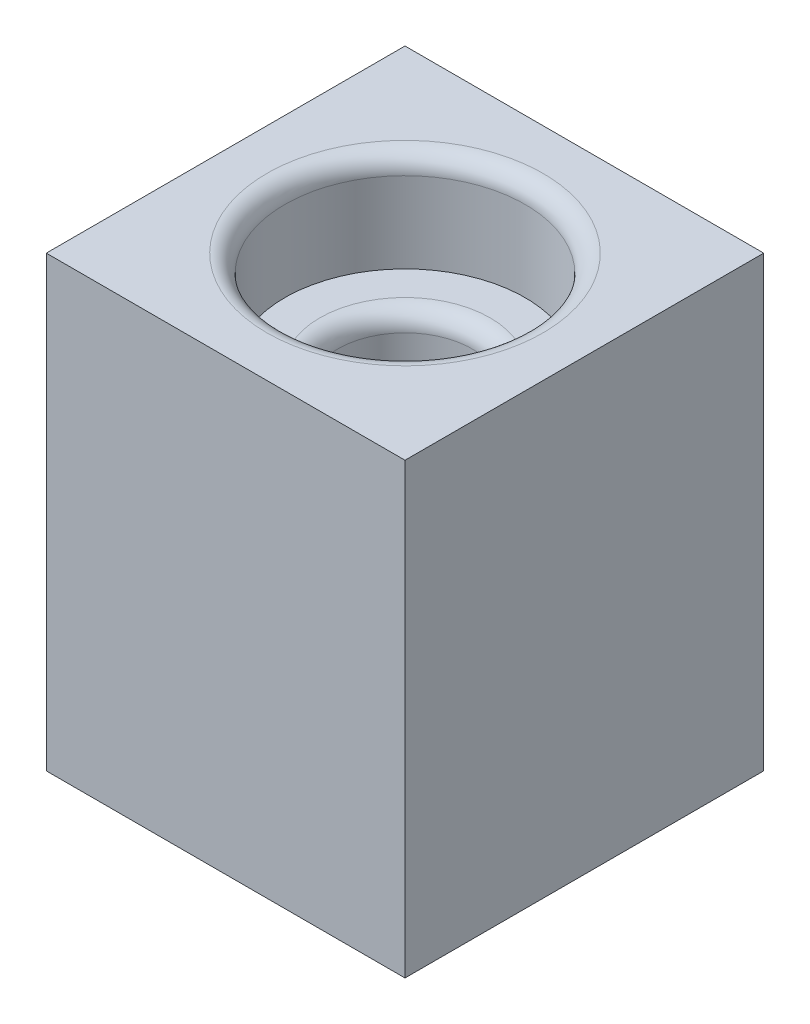
SolidWorks part; units mm, degrees
ref_plane "Ebene vorne" through (0, 0, 0) normal (0, 0, 1) x (1, 0, 0)
ref_plane "Ebene oben" through (0, 0, 0) normal (0, 1, 0) x (1, 0, 0)
ref_plane "Ebene rechts" through (0, 0, 0) normal (1, 0, 0) x (0, 0, -1)
sketch "Sketch3" plane through (0, 0, 0) normal (0, 1, 0) x (1, 0, 0)
  line L0 (0, 13.1643) -> (0, -11.9056) construction
  line L1 (-10, 10) -> (10, 10)
  line L2 (-10, 10) -> (-10, -10)
  line L3 (-10, -10) -> (10, -10)
  line L4 (10, 10) -> (10, -10)
  line L5 (-26.5385, 0) -> (29.5804, 0) construction
  dimension "D1" = 20
extrude "Boss-Extrude1" add sketch "Sketch3" along normal blind 25
sketch "Sketch4" plane through (0, 25, 0) normal (0, 1, 0) x (1, 0, 0)
  circle A0 centre (0, 0) radius 6.7
  circle A1 centre (0, 0) radius 3.75
  dimension "D1" = 13.4
  dimension "D2" = 7.5
extrude "Cut-Extrude1" cut sketch "Sketch4" against normal through all contours A1
extrude "Cut-Extrude2" cut sketch "Sketch4<3>" against normal blind 5.5 contours A0
sketch "Sketch4<3>" plane through (0, 25, 0) normal (0, 1, 0) x (1, 0, 0) same geometry as "Sketch4"
extrude "Cut-Extrude3" cut sketch "Sketch4<4>" along normal blind 5.5 from surface contours A0 starting at face at (0, 0, 3.75)
sketch "Sketch4<4>" plane through (0, 25, 0) normal (0, 1, 0) x (1, 0, 0) same geometry as "Sketch4"
fillet "Fillet1" radius 1 2 edges at (0, 0, 6.7) (0, 25, 6.7)
fillet "Fillet2" radius 1 2 edges at (0, 19.5, 3.75) (0, 5.5, 3.75)
